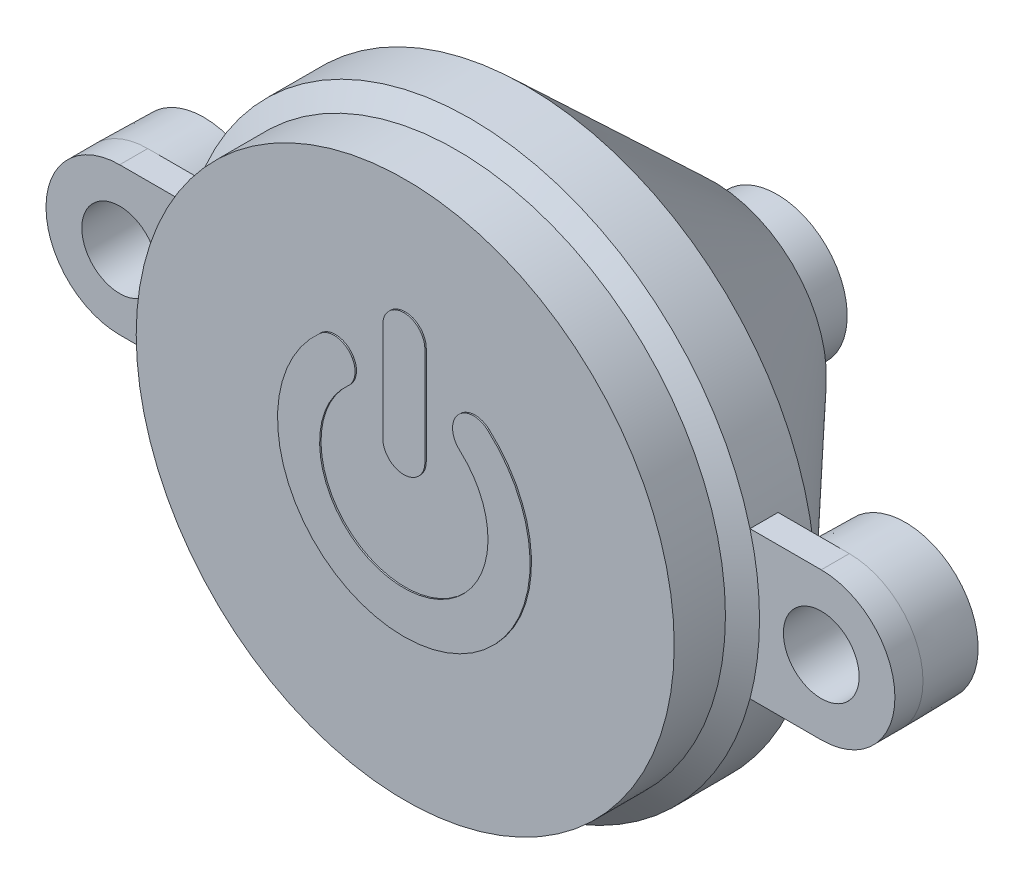
SolidWorks part; units mm, degrees
ref_plane "前视基准面" through (0, 0, 0) normal (0, 0, 1) x (1, 0, 0)
ref_plane "上视基准面" through (0, 0, 0) normal (0, 1, 0) x (1, 0, 0)
ref_plane "右视基准面" through (0, 0, 0) normal (1, 0, 0) x (0, 0, -1)
sketch "草图1" plane through (0, 0, 0) normal (0, 0, 1) x (1, 0, 0)
  circle A0 centre (0, 0) radius 20.6
  dimension "D1" = 41.2
extrude "凸台-拉伸1" add sketch "草图1" along normal blind 4
sketch "草图2" plane through (0, 0, 4) normal (0, 0, 1) x (1, 0, 0)
  circle A1 centre (0, 0) radius 20.6
  circle A2 centre (0, 0) radius 20.6
  dimension "D1" = 0
extrude "凸台-拉伸2" add sketch "草图2" along normal blind 1 draft 55
sketch "草图3" plane through (0, 0, 5) normal (0, 0, 1) x (1, 0, 0)
  circle A1 centre (0, 0) radius 19.1719
  circle A2 centre (0, 0) radius 19.1719
  dimension "D1" = 0
extrude "凸台-拉伸3" add sketch "草图3" along normal blind 3.65
sketch "草图4" plane through (0, 0, 0) normal (0, 0, -1) x (-1, 0, 0)
  circle A1 centre (0, 0) radius 20.6
  circle A2 centre (0, 0) radius 20.6
  dimension "D1" = 0
extrude "凸台-拉伸4" add sketch "草图4" along normal blind 13.35 draft 43.3
sketch "草图5" plane through (0, 0, -13.35) normal (0, 0, -1) x (-1, 0, 0)
  circle A0 centre (0, 0) radius 5
  circle A1 centre (0, 0) radius 3
  dimension "D1" = 10
  dimension "D2" = 6
extrude "凸台-拉伸5" add sketch "草图5" along normal blind 4.5
sketch "草图6" plane through (0, 0, 0) normal (0, 0, 1) x (1, 0, 0)
  line L0 (-25.4929, 0) -> (24.0053, 0) construction
  line L1 (0, 11.1236) -> (0, -10.8531) construction
  line L2 (25, 5.25) -> (19.0698, 5.25)
  line L3 (25, -5.25) -> (19.0698, -5.25)
  line L4 (19.0698, -5.25) -> (19.0698, 5.25)
  arc A0 (25, -5.25) -> (25, 5.25) centre (25, 0) ccw
  dimension "D1" = 10.5
  dimension "D2" = 5.25
  dimension "D3" = 25
extrude "凸台-拉伸6" add sketch "草图6" along normal blind 2 from offset 2
sketch "草图7" plane through (0, 0, 2) normal (0, 0, -1) x (-1, 0, 0)
  circle A0 centre (-25, 0) radius 5.25
extrude "凸台-拉伸8" add sketch "草图7" along normal blind 4 draft 1
sketch "草图8" plane through (0, 0, 4) normal (0, 0, 1) x (1, 0, 0)
  circle A0 centre (25, 0) radius 2.7
  dimension "D1" = 5.4
extrude "切除-拉伸1" cut sketch "草图8" against normal blind 4
sketch "草图9" plane through (0, 0, 0) normal (0, 0, 1) x (1, 0, 0)
  circle A0 centre (25, 0) radius 1.6
  dimension "D1" = 3.2
extrude "切除-拉伸2" cut sketch "草图9" against normal blind 4
mirror "镜向1" about plane through (0, 0, 0) normal (1, 0, 0) of "凸台-拉伸6", "切除-拉伸2", "切除-拉伸1", "凸台-拉伸8"
sketch "草图10" plane through (0, 0, 8.65) normal (0, 0, 1) x (1, 0, 0)
  line L0 (0, 16.7341) -> (0, -14.7151) construction
  line L1 (0, 0) -> (4.5, 7.7942) construction
  line L2 (0, 0) -> (-4.5, 7.7942) construction
  line L3 (-3, 5.1962) -> (-4.5, 7.7942)
  line L4 (-1.5, 11) -> (1.5, 11)
  line L5 (-1.5, 11) -> (-1.5, 1)
  line L6 (-1.5, 1) -> (1.5, 1)
  line L7 (1.5, 11) -> (1.5, 1)
  line L8 (3, 5.1962) -> (4.5, 7.7942)
  arc A0 (-3, 5.1962) -> (3, 5.1962) centre (0, 0) ccw
  arc A1 (-4.5, 7.7942) -> (4.5, 7.7942) centre (0, 0) ccw
  circle A3 centre (0, 0) radius 6 construction
  circle A4 centre (0, 0) radius 9 construction
  point P1 (12, 0)
  point P9 (9.563, 2.9237)
  dimension "D1" = 12
  dimension "D3" = 30
  dimension "D4" = 3
  dimension "D5" = 1.5
  dimension "D6" = 10
  dimension "D7" = 1
  dimension "D2" = 3
extrude "凸台-拉伸9" add sketch "草图10" along normal blind 0.1
fillet "圆角1" radius 1.5 8 edges at (-3, 5.1962, 8.7) (-4.5, 7.7942, 8.7) (1.5, 1, 8.7) (-1.5, 1, 8.7) (1.5, 11, 8.7) (-1.5, 11, 8.7) (4.5, 7.7942, 8.7) (3, 5.1962, 8.7)
